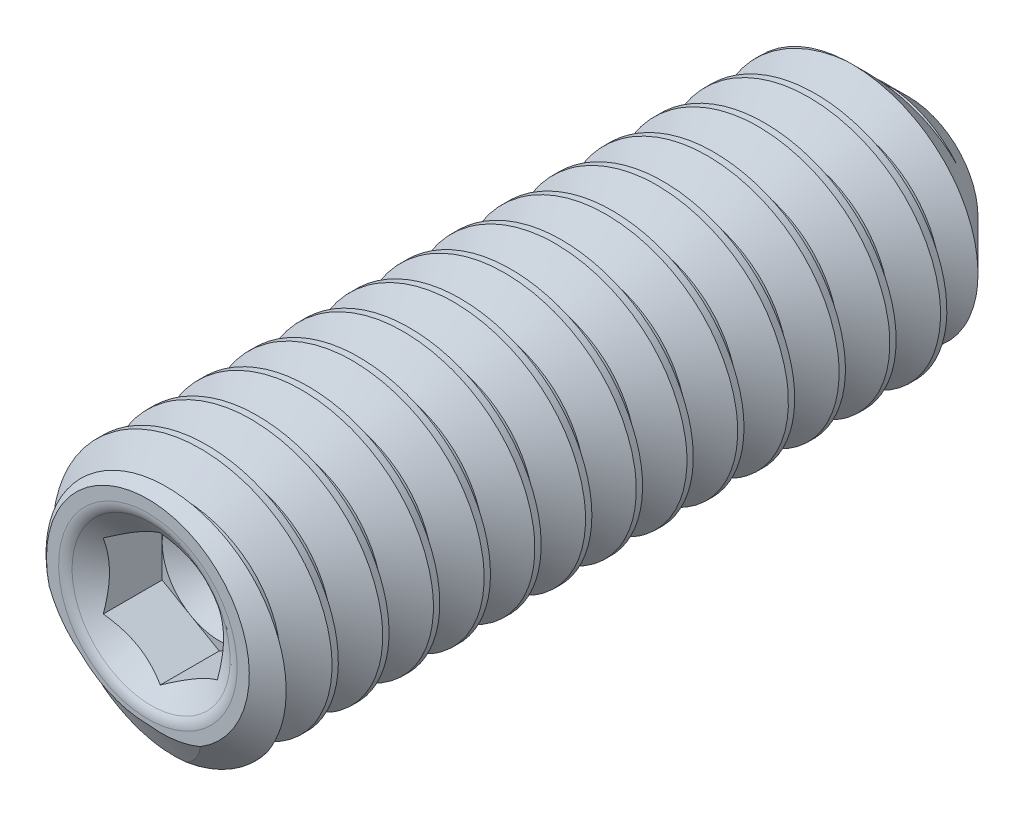
SolidWorks part; units mm, degrees
ref_plane "Front" through (0, 0, 0) normal (0, 0, 1) x (1, 0, 0)
ref_plane "Top" through (0, 0, 0) normal (0, 1, 0) x (1, 0, 0)
ref_plane "Right" through (0, 0, 0) normal (1, 0, 0) x (0, 0, -1)
sketch "Sketch22" plane through (0, 0, 0) normal (1, 0, 0) x (0, 0, -1)
  line L0 (-2.8354, 0) -> (-2.8354, 0.8)
  line L1 (-2.8354, 0.8) -> (-2.6953, 1)
  line L2 (-2.6953, 1) -> (2.7126, 1)
  line L3 (2.7126, 1) -> (3.1646, 0.548)
  line L4 (3.1646, 0.548) -> (2.8354, 0)
  line L5 (2.8354, 0) -> (-2.8354, 0)
  line L6 (2.8354, 0) -> (3.1646, 0) construction
  line L7 (3.1646, 0) -> (3.1646, 0.548) construction
  line L8 (3.1646, -0.548) -> (2.8354, 0) construction
  line L9 (-2.6953, -1) -> (2.7126, -1) construction
  dimension "Dia" = 2
  dimension "Length" = 6
  dimension "D3" = 35
  dimension "D5" = 118
  dimension "D6" = 45
  dimension "D7" = 1.6
revolve "Revolve1" add sketch "Sketch22" angle 360 about L6
ref_plane "Plane1" through (0, 0, -3.1646) normal (0, 0, 1) x (1, 0, 0)
sketch "Sketch27" plane through (0, 0, -3.1646) normal (0, 0, 1) x (1, 0, 0)
  circle A0 centre (0, 0) radius 1 construction
  circle A1 centre (0, 0) radius 1
curve "Helix/Spiral1" pitch 0.4 height 6.4 radius 1 centre (0, 0, -3.1646) axis (0, 0, 1) start towards (0, 1, 0)
sketch "Sketch28" plane through (0, 0, 0) normal (1, 0, 0) x (0, 0, -1)
  line L0 (3.1646, 1) -> (3.5146, 1)
  line L1 (3.5146, 1) -> (3.3646, 0.7402)
  line L2 (3.3646, 0.7402) -> (3.3146, 0.7402)
  line L3 (3.3146, 0.7402) -> (3.1646, 1)
  line L4 (3.2396, 0.8701) -> (3.4396, 0.8701) construction
  line L6 (-2.6953, 1) -> (2.7126, 1) construction
  dimension "D1" = 0.05
  dimension "D3" = 60
  dimension "D2" = 0.2
sweep "Cut-Sweep2" cut profiles "Sketch28" path "Helix/Spiral1" align with end faces yes
sketch "Sketch23" plane through (0, 0, 2.8354) normal (0, 0, 1) x (1, 0, 0)
  line L1 (0, 0.5196) -> (-0.45, 0.2598)
  line L2 (-0.45, 0.2598) -> (-0.45, -0.2598)
  line L3 (-0.45, -0.2598) -> (0, -0.5196)
  line L4 (0, -0.5196) -> (0.45, -0.2598)
  line L5 (0.45, -0.2598) -> (0.45, 0.2598)
  line L6 (0.45, 0.2598) -> (0, 0.5196)
  circle A0 centre (0, 0) radius 0.45 construction
  dimension "Hex" = 0.9
extrude "Cut-Extrude10" cut sketch "Sketch23" against normal blind 0.5625
sketch "Sketch24" plane through (0, 0, 2.8354) normal (0, 0, 1) x (1, 0, 0)
  line L0 (0, 0.5196) -> (0, 0.8) construction
  circle A0 centre (0, 0) radius 0.6598
  point P5 (0, 0.6598)
  dimension "D1" = 0.1402
extrude "Cut-Extrude11" cut sketch "Sketch24" against normal through all draft 55
sketch "Sketch26" plane through (0, 0, 2.2729) normal (0, 0, 1) x (1, 0, 0)
  circle A0 centre (0, 0) radius 0.45 construction
  circle A1 centre (0, 0) radius 0.45
extrude "Cut-Extrude12" cut sketch "Sketch26" against normal through all draft 60
sketch "Sketch30" plane through (0, 0, 0) normal (1, 0, 0) x (0, 0, -1)
  line L0 (-2.6953, 1) -> (2.7126, 1) construction
  line L1 (-2.8354, 0) -> (-2.8354, 0.8) construction
  line L2 (3.1646, 0) -> (3.1646, 0.548) construction
  line L3 (-2.6953, -1) -> (2.7126, -1) construction
  point P0 (-2.8354, 1)
  point P1 (3.1646, 1)
  point P2 (3.1646, -1)
  point P11 (2.1646, -1)
  dimension "D1" = 1
sketch "Sketch31" plane through (0, 0, 0) normal (1, 0, 0) x (0, 0, -1)
  line L2 (2.8354, 0) -> (3.1646, -0.548)
  line L3 (3.1646, 0.548) -> (2.8354, 0)
fillet "Fillet2" radius 0.1402 1 edges at (0.6598, 0, 2.8354)
equation "\"D7@Sketch22\"=\"Dia@Sketch22\"*.8"
equation "\"D1@Sketch28\" = \"D4@Helix/Spiral1\" * .125"
equation "\"D2@Sketch28\" = \"D4@Helix/Spiral1\" * .5"
equation "\"D3@Helix/Spiral1\" = \"Length@Sketch22\" + \"D4@Helix/Spiral1\""
equation "\"D1@Sketch30\" = \"D4@Helix/Spiral1\" * 2.5"
equation "\"hex Depth@Cut-Extrude10\" = \"Hex@Sketch23\" * .625"
equation "\"D1@Fillet2\" = \"D1@Sketch24\""
